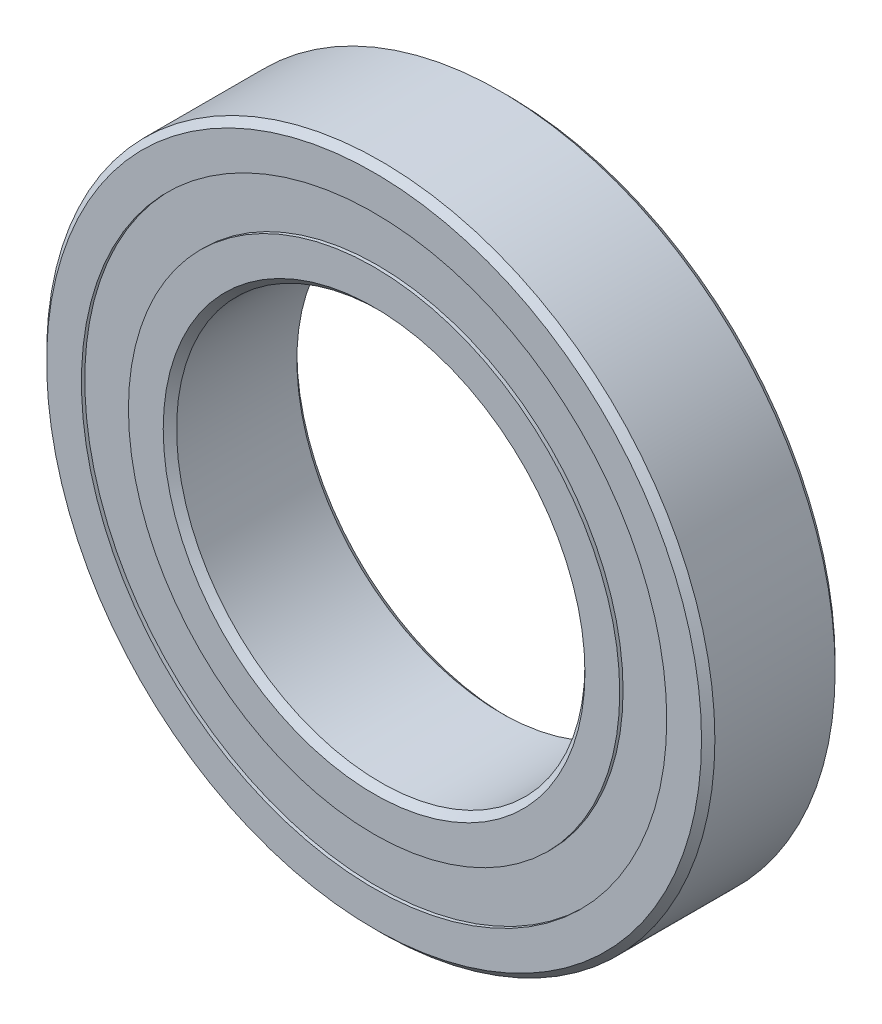
SolidWorks part; units mm, degrees
ref_plane "Front Plane" through (0, 0, 0) normal (0, 0, 1) x (1, 0, 0)
ref_plane "Top Plane" through (0, 0, 0) normal (0, 1, 0) x (1, 0, 0)
ref_plane "Right Plane" through (0, 0, 0) normal (1, 0, 0) x (0, 0, -1)
sketch "Sketch1" plane through (0, 0, 0) normal (1, 0, 0) x (0, 0, -1)
  line L0 (-9, 0) -> (9, 0) construction
  line L1 (0, 45) -> (0, -45) construction
  line L2 (8.1, 45) -> (-8.1, 45)
  line L3 (-8.1, 45) -> (-9, 44.1)
  line L4 (-9, 44.1) -> (-9, 39.4148)
  line L5 (-9, 39.4148) -> (-4, 39.4148)
  line L6 (9, 39.4148) -> (4, 39.4148)
  line L7 (9, 44.1) -> (9, 39.4148)
  line L8 (8.1, 45) -> (9, 44.1)
  line L9 (0, 45) -> (0, 36.25) construction
  line L10 (0, 36.25) -> (0, 27.5) construction
  arc A0 (-4, 39.4148) -> (4, 39.4148) centre (0, 36.25) cw
  point P14 (0, 27.5)
  dimension "Width" = 18
  dimension "OD" = 90
  dimension "D1" = 45
  dimension "D2" = 0.9
  dimension "Shaft Dia" = 55
  dimension "D3" = 8
  dimension "D4" = 3.1648
revolve "Revolve1" add sketch "Sketch1" angle 360 about L0
sketch "Sketch3" plane through (0, 0, 0) normal (1, 0, 0) x (0, 0, -1)
  line L0 (-9, 33.0852) -> (-4, 33.0852)
  line L1 (0, 45) -> (0, -45) construction
  line L2 (-9, 44.1) -> (-9, 39.4148) construction
  line L3 (-9, 33.0852) -> (-9, 28.4)
  line L4 (-8.1, 45) -> (-9, 44.1) construction
  line L5 (-9, 28.4) -> (-8.1, 27.5)
  line L6 (-8.1, 27.5) -> (8.1, 27.5)
  line L7 (8.1, 45) -> (8.1, -45) construction
  line L8 (8.1, 27.5) -> (9, 28.4)
  line L9 (9, -44.1) -> (9, 44.1) construction
  line L10 (9, 28.4) -> (9, 33.0852)
  line L11 (9, 33.0852) -> (4, 33.0852)
  line L13 (8.1, 45) -> (9, 44.1) construction
  arc A0 (4, 39.4148) -> (-4, 39.4148) centre (0, 36.25) ccw construction
  arc A1 (4, 33.0852) -> (-4, 33.0852) centre (0, 36.25) cw
revolve "Revolve3" add sketch "Sketch3" angle 360 about L0
sketch "Sketch4" plane through (0, 0, 0) normal (1, 0, 0) x (0, 0, -1)
  line L0 (-5.1006, 36.25) -> (5.1006, 36.25)
  arc A2 (-5.1006, 36.25) -> (5.1006, 36.25) centre (0, 36.25) cw
  arc A3 (4, 39.4148) -> (-4, 39.4148) centre (0, 36.25) ccw construction
revolve "Revolve4" add sketch "Sketch4" angle 360 about L0
ref_axis "Axis1" through (0, 0, -9) along (0, 0, 1)
pattern_circular "CirPattern1" count 12 every 30 about axis through (0, 0, -9) along (0, 0, 1) of bodies 104
sketch "Sketch5" plane through (0, 0, 0) normal (1, 0, 0) x (0, 0, -1)
  line L0 (-9, 39.4148) -> (-4, 39.4148) construction
  line L1 (-8.55, 39.4148) -> (-5.1006, 39.4148)
  line L2 (-8.55, 39.4148) -> (-8.55, 33.0852)
  line L3 (-8.55, 33.0852) -> (-5.1006, 33.0852)
  line L4 (-5.1006, 39.4148) -> (-5.1006, 33.0852)
  line L5 (-9, 33.0852) -> (-4, 33.0852) construction
  line L6 (9, 39.4148) -> (4, 39.4148) construction
  line L7 (8.55, 39.4148) -> (5.1006, 39.4148)
  line L8 (8.55, 39.4148) -> (8.55, 33.0852)
  line L9 (8.55, 33.0852) -> (5.1006, 33.0852)
  line L10 (5.1006, 39.4148) -> (5.1006, 33.0852)
  line L11 (9, 33.0852) -> (4, 33.0852) construction
  line L12 (-8.1, 45) -> (-9, 44.1) construction
  point P18 (-8.55, 44.55)
revolve "Revolve5" add sketch "Sketch5" angle 360 about L0
equation "\"D2@Sketch1\" = \"Width@Sketch1\"*.05"
equation "\"D3@Sketch1\" = \"Width@Sketch1\"/2.25"
equation "\"D4@Sketch1\" = (((\"OD@Sketch1\"-\"Width@Sketch1\")/2)/3.25)/3.5"
equation "\"D2@CirPattern1\" = 360/\"Balls@CirPattern1\""
